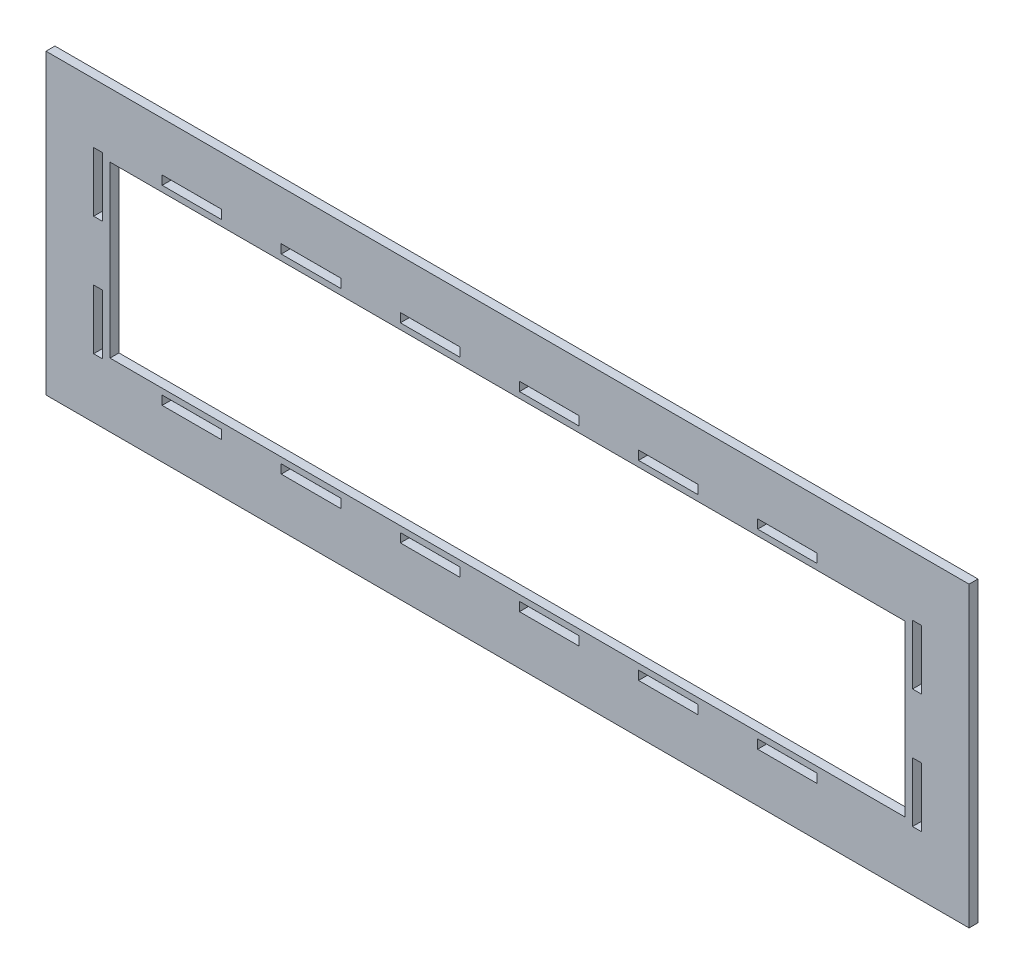
SolidWorks part; units mm, degrees
material "Balsa"
ref_plane "Alzado" through (0, 0, 0) normal (0, 0, 1) x (1, 0, 0)
ref_plane "Planta" through (0, 0, 0) normal (0, 1, 0) x (1, 0, 0)
ref_plane "Vista lateral" through (0, 0, 0) normal (1, 0, 0) x (0, 0, -1)
sketch "Croquis1" plane through (0, 0, 0) normal (0, 0, 1) x (1, 0, 0)
  line L1 (-310, 100) -> (310, 100)
  line L2 (-310, 100) -> (-310, -100)
  line L3 (-310, -100) -> (310, -100)
  line L4 (310, 100) -> (310, -100)
  line L5 (-310, 100) -> (310, -100) construction
  line L6 (-310, -100) -> (310, 100) construction
  line L7 (267, 57) -> (-267, 57)
  line L8 (267, 57) -> (267, -57)
  line L9 (267, -57) -> (-267, -57)
  line L10 (-267, 57) -> (-267, -57)
  line L11 (267, 57) -> (-267, -57) construction
  line L12 (267, -57) -> (-267, 57) construction
  point P0 (0, 0)
  point P6 (0, 0)
  dimension "D1" = 620
  dimension "D2" = 200
  dimension "D3" = 534
  dimension "D4" = 114
extrude "Saliente-Extruir1" add sketch "Croquis1" along normal blind 6
sketch "Croquis2" plane through (0, 0, 6) normal (0, 0, 1) x (1, 0, 0)
  line L0 (-267, 57) -> (-267, -57) construction
  line L1 (-278.02, 60) -> (-272, 60) construction
  line L2 (-278.02, 60) -> (-278.02, -60) construction
  line L3 (-278.02, -60) -> (-272, -60) construction
  line L4 (-272, 60) -> (-272, -60) construction
  line L5 (-278.02, 60) -> (-272, -60) construction
  line L6 (-278.02, -60) -> (-272, 60) construction
  line L7 (0, 126.1217) -> (0, -145.5943) construction
  line L8 (278.02, -60) -> (272, -60) construction
  line L9 (-278.02, 60) -> (-272, 60)
  line L10 (-278.02, 60) -> (-278.02, 20)
  line L11 (-278.02, 20) -> (-272, 20)
  line L12 (-272, 60) -> (-272, 20)
  line L13 (-278.02, -60) -> (-272, -60)
  line L14 (-278.02, -60) -> (-278.02, -20)
  line L15 (-278.02, -20) -> (-272, -20)
  line L16 (-272, -60) -> (-272, -20)
  line L17 (272, -60) -> (272, -20)
  line L18 (278.02, -20) -> (272, -20)
  line L19 (278.02, -60) -> (278.02, -20)
  line L20 (278.02, -60) -> (272, -60)
  line L21 (278.02, 60) -> (272, 60) construction
  line L22 (272, 60) -> (272, 20)
  line L23 (278.02, 20) -> (272, 20)
  line L24 (278.02, 60) -> (278.02, 20)
  line L25 (278.02, 60) -> (272, 60)
  line L26 (-67.9607, 0) -> (71.0745, 0) construction
  point P0 (-275.01, 0)
  point P8 (-267, 0)
  dimension "D1" = 6.02
  dimension "D2" = 120
  dimension "D3" = 5
  dimension "D4" = 40
  dimension "D5" = 40
extrude "Cortar-Extruir1" cut sketch "Croquis2" against normal blind 6
sketch "Croquis3" plane through (0, 0, 6) normal (0, 0, 1) x (1, 0, 0)
  line L1 (-232, 67.02) -> (-192, 67.02)
  line L2 (-232, 67.02) -> (-232, 61)
  line L3 (-232, 61) -> (-192, 61)
  line L4 (-192, 67.02) -> (-192, 61)
  line L5 (-272, 20) -> (-272, 60) construction
  dimension "D1" = 6.02
  dimension "D2" = 40
  dimension "D3" = 61
  dimension "D4" = 40
extrude "Cortar-Extruir2" cut sketch "Croquis3" against normal blind 6
pattern_linear "MatrizL1" count 6 spacing 80 along (1, 0, 0) of "Cortar-Extruir2"
mirror "Simetría1" about plane through (0, 0, 0) normal (0, 1, 0) of "MatrizL1"
